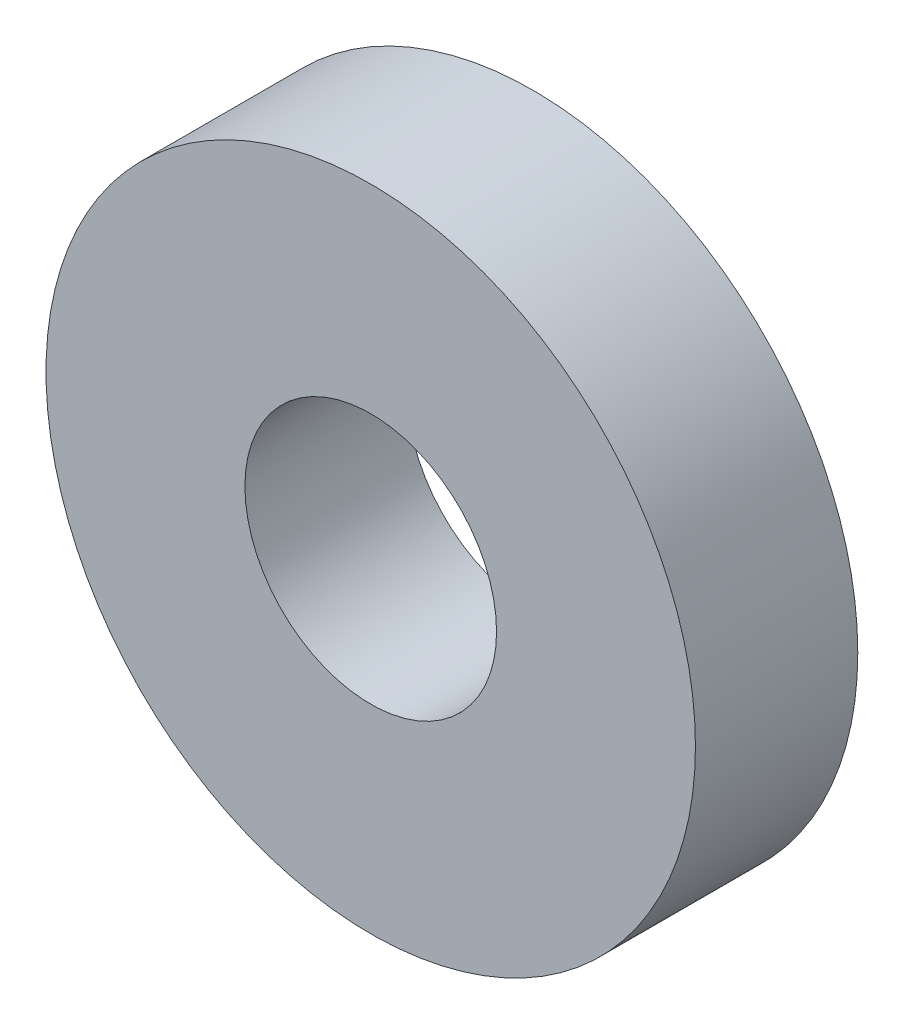
SolidWorks part; units mm, degrees
material "ABS"
ref_plane "Front Plane" through (0, 0, 0) normal (0, 0, 1) x (1, 0, 0)
ref_plane "Top Plane" through (0, 0, 0) normal (0, 1, 0) x (1, 0, 0)
ref_plane "Right Plane" through (0, 0, 0) normal (1, 0, 0) x (0, 0, -1)
sketch "Sketch1" plane through (0, 0, 0) normal (0, 0, 1) x (1, 0, 0)
  circle A0 centre (0, 0) radius 4
  dimension "D1" = 8
extrude "Boss-Extrude1" add sketch "Sketch1" along normal blind 2
sketch "Sketch2" plane through (0, 0, 2) normal (0, 0, 1) x (1, 0, 0)
  point P0 (0, 0)
hole_wizard "M2.5 Clearance Hole1" positions "Sketch2" profile "Sketch3" hole size "M2.5" standard "ANSI Metric" end condition through all
sketch "Sketch3" plane through (0, 0, 2) normal (1, 0, 0) x (0, -1, 0)
  line L0 (0, 0) -> (0, 2)
  line L1 (0, 2) -> (1.55, 2)
  line L2 (1.55, 2) -> (1.55, 0)
  line L5 (1.55, 0) -> (0, 0)
  line L11 (0, -6.35) -> (0, 107.95) construction
  dimension "Thru Hole Dia." = 3.1
  dimension "Thru Hole Depth" = 2
